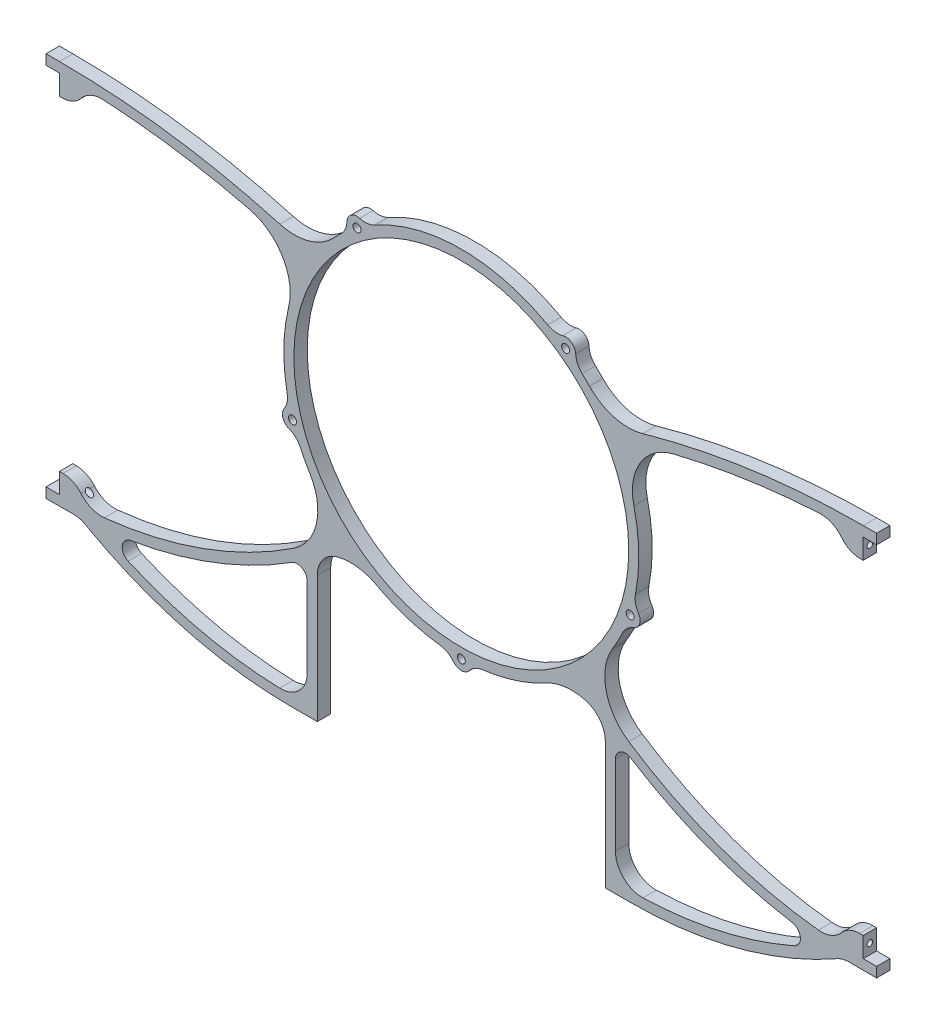
SolidWorks part; units mm, degrees
material "6061-T6 (SS)"
ref_plane "Front Plane" through (0, 0, 0) normal (0, 0, 1) x (1, 0, 0)
ref_plane "Top Plane" through (0, 0, 0) normal (0, 1, 0) x (1, 0, 0)
ref_plane "Right Plane" through (0, 0, 0) normal (1, 0, 0) x (0, 0, -1)
sketch "Sketch1" plane through (0, 0, 0) normal (0, 0, 1) x (1, 0, 0)
  line L0 (0, 0) -> (0, 155.0019) construction
  line L1 (0, 0) -> (247.3458, 0) construction
  line L2 (0, 63.5) -> (-209.2039, 63.5) construction
  line L3 (-190.5, 65.8813) -> (-190.5, 61.1187)
  line L4 (-107.6056, -114.3) -> (-205.432, -114.3) construction
  line L5 (-190.5, -111.9187) -> (-196.85, -111.9187)
  line L6 (190.5, 65.8813) -> (190.5, 61.1188)
  line L7 (-196.85, -111.9187) -> (-196.85, -116.6812)
  line L8 (-190.5, 61.1187) -> (-196.85, 61.1188)
  line L9 (-190.5, 61.1187) -> (-190.5, 65.8813)
  line L10 (-190.5, 65.8813) -> (-196.85, 65.8813)
  line L11 (-196.85, 61.1188) -> (-196.85, 65.8813)
  line L12 (-196.85, -116.6812) -> (-190.5, -116.6812)
  line L13 (-190.5, -111.9187) -> (-190.5, -116.6812)
  line L14 (190.5, -111.9187) -> (190.5, -116.6812)
  line L15 (196.85, -116.6812) -> (190.5, -116.6812)
  line L16 (196.85, -111.9187) -> (196.85, -116.6812)
  line L17 (190.5, 65.8813) -> (196.85, 65.8813)
  line L18 (196.85, 61.1188) -> (196.85, 65.8813)
  line L19 (190.5, 61.1188) -> (196.85, 61.1188)
  line L21 (190.5, -111.9187) -> (196.85, -111.9187)
  circle A0 centre (0, 0) radius 79.375
  arc A1 (0, 12.4557) -> (-190.5, 63.5) centre (-190.5, -317.5) ccw construction
  arc A2 (-70.1249, 46.4932) -> (-190.5, 65.8813) centre (-190.5, -317.5) ccw
  arc A3 (-72.7131, 42.3311) -> (-190.5, 61.1187) centre (-190.5, -317.5) ccw
  arc A4 (1.1906, 14.5179) -> (-190.5, 65.8813) centre (-190.5, -317.5) ccw construction
  arc A5 (-1.1906, 10.3935) -> (-190.5, 61.1187) centre (-190.5, -317.5) ccw construction
  circle A6 centre (0, 0) radius 84.1375
  arc A7 (-190.5, -116.6812) -> (-53.8243, -64.6689) centre (-190.5, 88.9) ccw
  arc A8 (-190.5, -111.9187) -> (-57.4233, -61.4954) centre (-190.5, 88.9) ccw
  arc A9 (-190.5, -116.6812) -> (-32.5894, -42.7355) centre (-190.5, 88.9) ccw construction
  arc A10 (-190.5, -111.9187) -> (-36.2476, -39.686) centre (-190.5, 88.9) ccw construction
  arc A11 (72.7131, 42.3311) -> (190.5, 61.1188) centre (190.5, -317.5) cw
  arc A12 (70.1249, 46.4932) -> (190.5, 65.8813) centre (190.5, -317.5) cw
  arc A13 (-190.5, -114.3) -> (-55.6494, -63.1051) centre (-190.5, 88.9) ccw construction
  arc A14 (-190.5, -114.3) -> (-34.4185, -41.2108) centre (-190.5, 88.9) ccw construction
  arc A15 (190.5, -114.3) -> (55.6494, -63.1051) centre (190.5, 88.9) cw construction
  arc A16 (190.5, -111.9187) -> (57.4233, -61.4954) centre (190.5, 88.9) cw
  arc A17 (190.5, -116.6812) -> (53.8243, -64.6689) centre (190.5, 88.9) cw
  point P55 (0, 12.4557)
  dimension "D1" = 158.75
  dimension "D2" = 381
  dimension "D4" = 2.3813
  dimension "D6" = 4.7625
  dimension "D8" = 203.2
  dimension "D12" = 381
  dimension "D3" = 2.3813
  dimension "D7" = 6.35
  dimension "D5" = 63.5
  dimension "D9" = 177.8
  dimension "D10" = 2.3813
  dimension "D11" = 2.3813
extrude "Boss-Extrude1" add sketch "Sketch1" along normal blind 6.35
fillet "Fillet1" radius 25.4 8 edges at (57.4233, -61.4954, 3.175) (53.8243, -64.6689, 3.175) (-53.8243, -64.6689, 3.175) (-57.4233, -61.4954, 3.175) (72.7131, 42.3311, 3.175) (70.1249, 46.4932, 3.175) (-70.1249, 46.4932, 3.175) (-72.7131, 42.3311, 3.175)
sketch "Sketch2" plane through (0, 0, 6.35) normal (0, 0, 1) x (1, 0, 0)
  line L0 (-190.5, 51.5938) -> (-190.5, 63.5)
  line L1 (-196.85, 63.5) -> (-190.5, 63.5) construction
  line L2 (-196.85, 61.1188) -> (-196.85, 65.8813) construction
  line L3 (-190.5, 63.5) -> (-190.5, 65.8813) construction
  line L4 (-190.5, 51.5938) -> (-182.5625, 51.5937)
  line L5 (-182.5625, 51.5937) -> (-182.5625, 63.5)
  line L6 (-190.5, 61.1187) -> (-196.85, 61.1188) construction
  line L7 (0, 0) -> (142.9721, 0) construction
  line L8 (0, 0) -> (0, 152.7746) construction
  line L9 (-190.5, 63.5) -> (-182.5625, 63.5)
  line L10 (-196.85, -114.3) -> (-175.6713, -114.3) construction
  line L11 (-196.85, -111.9187) -> (-196.85, -116.6812) construction
  line L12 (-190.5, -114.3) -> (-182.5625, -114.3)
  line L13 (-182.5625, -114.3) -> (-182.5625, -102.3937)
  line L14 (-182.5625, -102.3937) -> (-190.5, -102.3937)
  line L15 (-190.5, -102.3937) -> (-190.5, -114.3)
  line L16 (190.5, -102.3937) -> (190.5, -114.3)
  line L17 (182.5625, -102.3937) -> (190.5, -102.3937)
  line L18 (190.5, 63.5) -> (190.5, 65.8813) construction
  line L19 (196.85, 63.5) -> (190.5, 63.5) construction
  line L20 (190.5, 63.5) -> (182.5625, 63.5)
  line L21 (182.5625, 51.5937) -> (182.5625, 63.5)
  line L22 (190.5, 51.5938) -> (182.5625, 51.5937)
  line L23 (190.5, 51.5938) -> (190.5, 63.5)
  line L24 (182.5625, -114.3) -> (182.5625, -102.3937)
  line L25 (190.5, -114.3) -> (182.5625, -114.3)
  dimension "D1" = 9.525
  dimension "D2" = 7.9375
extrude "Boss-Extrude3" add sketch "Sketch2" against normal through all
fillet "Fillet3" radius 12.7 4 edges at (182.5625, -111.7618, 3.175) (-182.5625, -111.7618, 3.175) (182.5625, 61.0355, 3.175) (-182.5625, 61.0355, 3.175)
fillet "Fillet4" radius 11.1125 4 edges at (182.5625, -102.3937, 3.175) (-182.5625, -102.3937, 3.175) (182.5625, 51.5937, 3.175) (-182.5625, 51.5937, 3.175)
hole_wizard "#6-32 Tapped Hole1" positions "Sketch4" profile "Sketch5" tap size "#6-32" standard "ANSI Inch" end condition up to next
sketch "Sketch4" plane through (190.5, 0, 0) normal (1, 0, 0) x (0, 0, -1)
  line L3 (-3.175, 51.5938) -> (-3.175, 61.1188) construction
  line L4 (0, 51.5938) -> (-6.35, 51.5938) construction
  line L5 (-6.35, 61.1188) -> (0, 61.1188) construction
  line L6 (0, 0) -> (63.168, 0) construction
  line L7 (-6.35, -107.1562) -> (0, -107.1562) construction
  line L8 (-6.35, -111.9187) -> (-6.35, -102.3937) construction
  line L9 (0, -111.9187) -> (0, -102.3937) construction
  point P16 (-3.175, 56.3563)
  point P24 (-3.175, -107.1562)
sketch "Sketch5" plane through (190.5, 56.3563, 3.175) normal (0, 1, 0) x (0, 0, -1)
  line L0 (0, 0) -> (0, 84.9275)
  line L1 (0, 84.9275) -> (1.3525, 84.9275)
  line L2 (1.3525, 84.9275) -> (1.3525, 0)
  line L5 (1.3525, 0) -> (0, 0)
  line L11 (0, -6.35) -> (0, 107.95) construction
  dimension "Thread Major Dia." = 2.7051
  dimension "Thru Tap Drill Depth" = 84.9275
mirror "Mirror1" about plane through (0, 0, 0) normal (1, 0, 0) of "#6-32 Tapped Hole1"
sketch "Sketch10" plane through (0, 0, 6.35) normal (0, 0, 1) x (1, 0, 0)
  line L0 (-70.6438, -78.1273) -> (-70.6438, -141.6273) construction
  line L1 (-70.6438, -141.6273) -> (-80.1688, -141.6273) construction
  line L2 (0, 0) -> (0, -202.1798) construction
  line L3 (-68.2625, -144.0086) -> (-80.1688, -144.0086)
  line L4 (-68.2625, -76.3926) -> (-68.2625, -144.0086)
  line L5 (-73.025, -139.2461) -> (-80.1688, -139.2461)
  line L6 (-73.025, -79.8106) -> (-73.025, -139.2461)
  line L7 (-68.2625, -78.1273) -> (-68.2625, -144.0086) construction
  line L8 (-73.025, -78.1273) -> (-73.025, -139.2461) construction
  line L9 (70.6438, -141.6273) -> (80.1688, -141.6273) construction
  line L10 (70.6438, -78.1273) -> (70.6438, -141.6273) construction
  line L11 (73.025, -79.8106) -> (73.025, -139.2461)
  line L12 (73.025, -139.2461) -> (80.1688, -139.2461)
  line L13 (68.2625, -76.3926) -> (68.2625, -144.0086)
  line L14 (68.2625, -144.0086) -> (80.1688, -144.0086)
  arc A0 (-190.5, -116.6812) -> (-67.5452, -75.8597) centre (-190.5, 88.9) ccw construction
  arc A1 (-176.6452, -116.2139) -> (-80.1688, -141.6273) centre (-80.1688, 54.2046) ccw
  arc A2 (-180.975, -116.4605) -> (-172.3385, -115.8775) centre (-190.5, 88.9) ccw
  arc A3 (-180.975, -116.4605) -> (-80.1688, -144.0086) centre (-80.1688, 54.2046) ccw
  arc A4 (-172.3385, -115.8775) -> (-80.1688, -139.2461) centre (-80.1688, 54.2046) ccw
  arc A5 (-177.8183, -118.2861) -> (-80.1688, -144.0086) centre (-80.1688, 54.2046) ccw construction
  arc A6 (-175.472, -114.1416) -> (-80.1688, -139.2461) centre (-80.1688, 54.2046) ccw construction
  arc A7 (-73.025, -79.8106) -> (-68.2625, -76.3926) centre (-190.5, 88.9) ccw
  arc A8 (73.025, -79.8106) -> (68.2625, -76.3926) centre (190.5, 88.9) cw
  arc A9 (172.3385, -115.8775) -> (80.1688, -139.2461) centre (80.1688, 54.2046) cw
  arc A10 (180.975, -116.4605) -> (80.1688, -144.0086) centre (80.1688, 54.2046) cw
  arc A11 (180.975, -116.4605) -> (172.3385, -115.8775) centre (190.5, 88.9) cw
  arc A12 (176.6452, -116.2139) -> (80.1688, -141.6273) centre (80.1688, 54.2046) cw
  dimension "D6" = 136.525
  dimension "D1" = 9.525
  dimension "D2" = 63.5
  dimension "D3" = 2.3813
  dimension "D5" = 9.525
  dimension "D4" = 2.3813
extrude "Boss-Extrude4" add sketch "Sketch10" against normal up to surface (6.35 mm away) up to face at (0, -20.7832, 0)
fillet "Fillet5" radius 12.7 6 edges at (-73.025, -139.2461, 3.175) (73.025, -139.2461, 3.175) (-180.975, -116.4605, 3.175) (180.975, -116.4605, 3.175) (68.2625, -76.3926, 3.175) (-68.2625, -76.3926, 3.175)
hole_wizard "#6 Clearance Hole1" positions "Sketch12" profile "Sketch13" hole size "#6" standard "ANSI Inch"
sketch "Sketch12" plane through (0, -144.0086, 0) normal (0, -1, 0) x (-1, 0, 0)
  line L0 (68.2625, -3.175) -> (112.5817, -3.175) construction
  line L1 (68.2625, 0) -> (68.2625, -6.35) construction
  line L3 (68.2625, 0) -> (68.2625, -6.35) construction
  line L4 (0, 0) -> (0, 23.4867) construction
  point P0 (73.7489, -3.175)
  point P18 (-73.7489, -3.175)
  dimension "D1" = 5.4864
sketch "Sketch13" plane through (-73.7489, -144.0086, 3.175) normal (1, 0, 0) x (0, 0, -1)
  line L0 (0, 0) -> (0, 8.7608)
  line L1 (0, 8.7608) -> (1.8986, 7.62)
  line L2 (1.8986, 7.62) -> (1.8986, 0)
  line L5 (1.8986, 0) -> (0, 0)
  line L10 (0, 8.7608) -> (-1.8987, 7.62) construction
  line L11 (0, -6.35) -> (0, 107.95) construction
  dimension "Hole Dia." = 3.7973
  dimension "Hole Depth" = 7.62
  dimension "Drill Angle" = 118
fillet "Fillet6" radius 4.7625 4 edges at (172.3385, -115.8775, 3.175) (73.025, -79.8106, 3.175) (-73.025, -79.8106, 3.175) (-172.3385, -115.8775, 3.175)
sketch "Sketch14" plane through (0, 0, 6.35) normal (0, 0, 1) x (1, 0, 0)
  line L1 (0, 0) -> (80.0195, -25.9999) construction
  line L2 (0, 0) -> (0, 107.5426) construction
  line L3 (0, 0) -> (49.4548, 68.0687) construction
  line L4 (0, 0) -> (0, -84.1375) construction
  circle A0 centre (0, 0) radius 84.1375 construction
  arc A1 (60.7374, 58.2245) -> (-60.7374, 58.2245) centre (0, 0) ccw construction
  circle A2 centre (-80.0195, -25.9999) radius 4.7625
  circle A3 centre (-49.4548, 68.0687) radius 4.7625
  circle A4 centre (49.4548, 68.0687) radius 4.7625
  circle A5 centre (0, 0) radius 79.375 construction
  circle A6 centre (0, -84.1375) radius 4.7625
  circle A8 centre (80.0195, -25.9999) radius 4.7625
  dimension "D1" = 9.525
  dimension "D3" = 72
  dimension "D2" = 72
extrude "Boss-Extrude5" add sketch "Sketch14" against normal up to surface (6.35 mm away) up to face at (-104.3244, -113.8828, 0)
hole_wizard "#6 Clearance Hole3" positions "Sketch16" profile "Sketch17" hole size "#6" standard "ANSI Inch"
sketch "Sketch16" plane through (0, 0, 6.35) normal (0, 0, 1) x (1, 0, 0)
  point P0 (-49.4548, 68.0687)
  point P3 (49.4548, 68.0687)
  point P6 (80.0195, -25.9999)
  point P9 (0, -84.1375)
  point P12 (-80.0195, -25.9999)
sketch "Sketch17" plane through (-49.4548, 68.0687, 6.35) normal (1, 0, 0) x (0, -1, 0)
  line L0 (0, 0) -> (0, 26.5408)
  line L1 (0, 26.5408) -> (1.8986, 25.4)
  line L2 (1.8986, 25.4) -> (1.8986, 0)
  line L5 (1.8986, 0) -> (0, 0)
  line L10 (0, 26.5408) -> (-1.8987, 25.4) construction
  line L11 (0, -6.35) -> (0, 107.95) construction
  dimension "Hole Dia." = 3.7973
  dimension "Hole Depth" = 25.4
  dimension "Drill Angle" = 118
fillet "Fillet7" radius 9.525 10 edges at (-45.5242, 70.7578, 3.175) (-53.227, 65.1614, 3.175) (53.227, 65.1614, 3.175) (45.5242, 70.7578, 3.175) (78.4202, -30.4859, 3.175) (81.3624, -21.4307, 3.175) (-4.7606, -84.0027, 3.175) (4.7606, -84.0027, 3.175) (-81.3624, -21.4307, 3.175) (-78.4202, -30.4859, 3.175)
